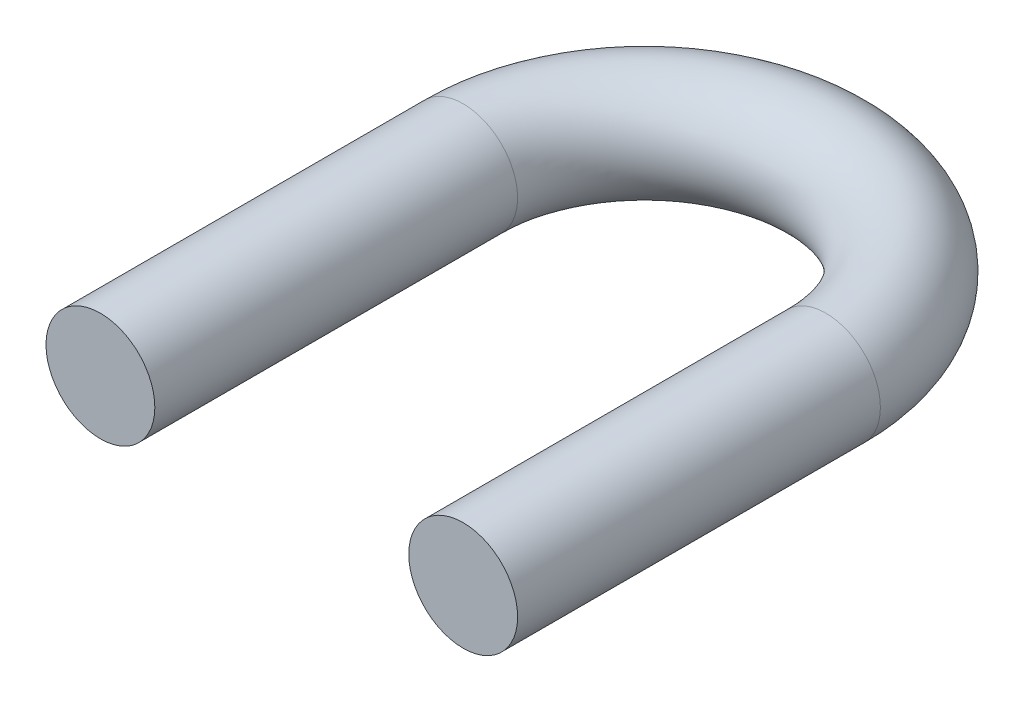
SolidWorks part; units mm, degrees
ref_plane "Front Plane" through (0, 0, 0) normal (0, 0, 1) x (1, 0, 0)
ref_plane "Top Plane" through (0, 0, 0) normal (0, 1, 0) x (1, 0, 0)
ref_plane "Right Plane" through (0, 0, 0) normal (1, 0, 0) x (0, 0, -1)
sketch "Sketch1" plane through (0, 0, 0) normal (0, 1, 0) x (1, 0, 0)
  line L0 (-10, 0) -> (-10, -20)
  line L1 (10, 0) -> (10, -20)
  arc A0 (10, 0) -> (-10, 0) centre (0, 0) ccw
  dimension "D1" = 20
  dimension "D2" = 20
sweep "Sweep1" add path "Sketch1" circular profile diameter 6 parameters "D3"=6
